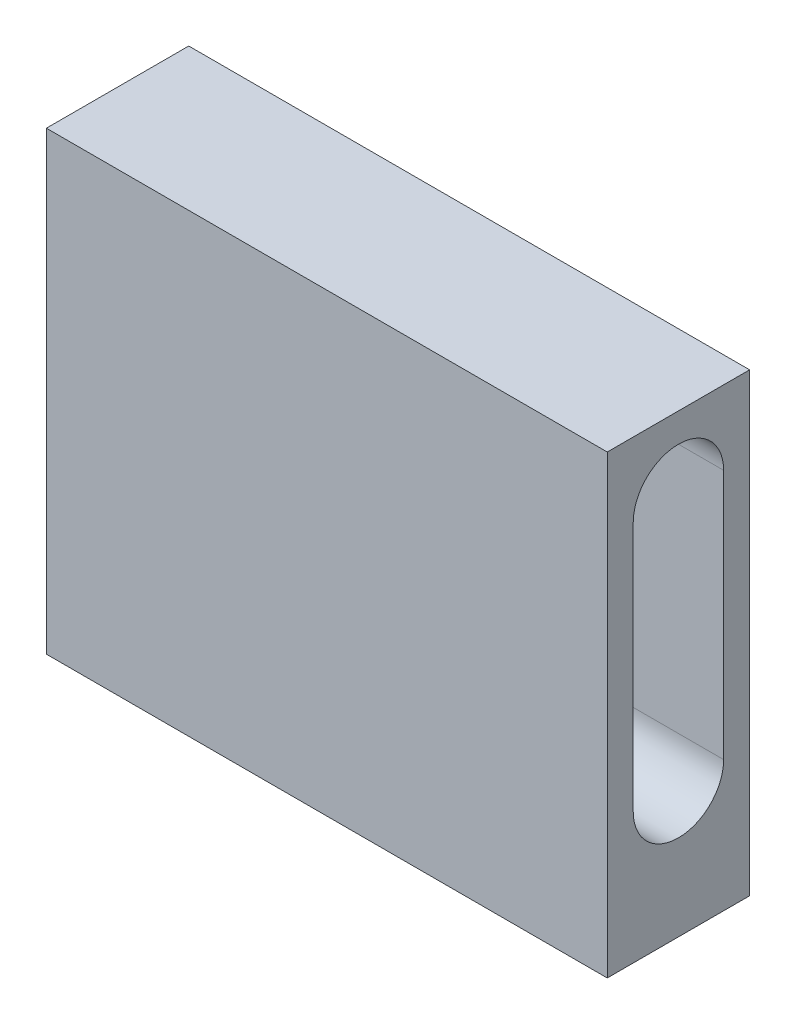
SolidWorks part; units mm, degrees
ref_plane "Front Plane" through (0, 0, 0) normal (0, 0, 1) x (1, 0, 0)
ref_plane "Top Plane" through (0, 0, 0) normal (0, 1, 0) x (1, 0, 0)
ref_plane "Right Plane" through (0, 0, 0) normal (1, 0, 0) x (0, 0, -1)
sketch "Sketch1" plane through (0, 0, 0) normal (0, 1, 0) x (1, 0, 0)
  line L1 (-9.85, -2.5) -> (9.85, -2.5)
  line L2 (-9.85, -2.5) -> (-9.85, 2.5)
  line L3 (-9.85, 2.5) -> (9.85, 2.5)
  line L4 (9.85, -2.5) -> (9.85, 2.5)
  line L5 (-9.85, -2.5) -> (9.85, 2.5) construction
  line L6 (-9.85, 2.5) -> (9.85, -2.5) construction
  point P0 (0, 0)
  dimension "D1" = 19.7
  dimension "D2" = 5
extrude "Boss-Extrude1" add sketch "Sketch1" along normal blind 14 contours L1 L4 L3 L2
sketch "Sketch2" plane through (9.85, 0, 0) normal (1, 0, 0) x (0, 0, -1)
  line L0 (2.5, 14) -> (-2.5, 0) construction
  line L1 (0, 2.6) -> (0, 11.4) construction
  line L2 (-1.5875, 2.6) -> (-1.5875, 11.4)
  line L3 (1.5875, 2.6) -> (1.5875, 11.4)
  arc A0 (-1.5875, 2.6) -> (1.5875, 2.6) centre (0, 2.6) ccw
  arc A1 (1.5875, 11.4) -> (-1.5875, 11.4) centre (0, 11.4) ccw
  point P6 (0, 7)
  dimension "D1" = 8.8
  dimension "D2" = 3.175
extrude "Cut-Extrude1" cut sketch "Sketch2" against normal blind 4
sketch "Sketch3" plane through (0, 0, 0) normal (0, -1, 0) x (1, 0, 0)
  line L4 (-9.85, 2.5) -> (-9.85, -2.5)
  line L5 (-9.85, -2.5) -> (9.85, -2.5)
  line L6 (9.85, -2.5) -> (9.85, 2.5)
  line L7 (9.85, 2.5) -> (-9.85, 2.5)
  line L8 (-9.85, 2.5) -> (-9.85, -2.5)
  line L9 (-9.85, -2.5) -> (9.85, -2.5)
  line L10 (9.85, -2.5) -> (9.85, 2.5)
  line L11 (9.85, 2.5) -> (-9.85, 2.5)
  dimension "D1" = 0
extrude "Boss-Extrude2" add sketch "Sketch3" along normal blind 2
